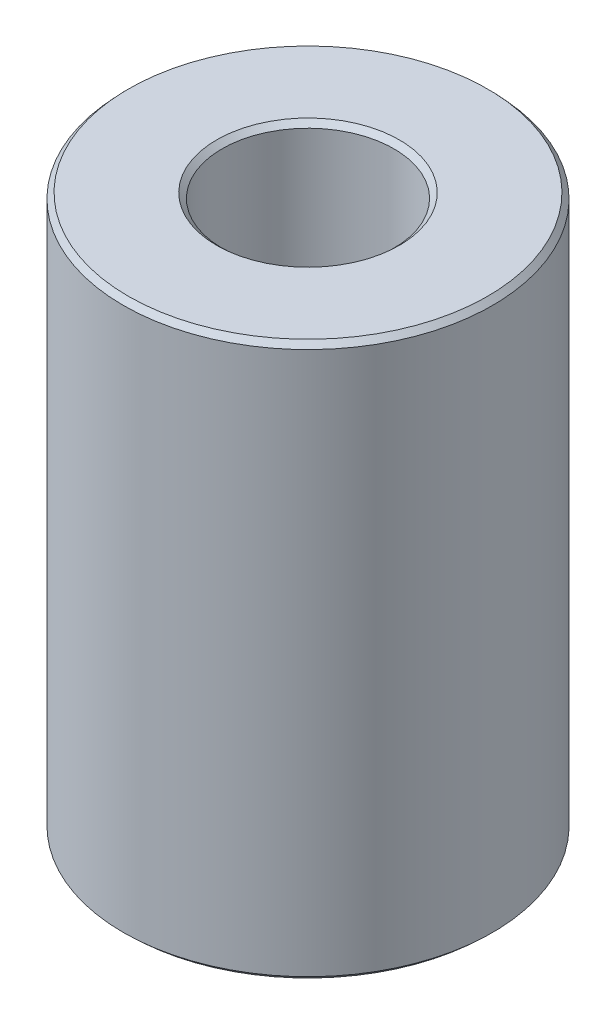
SolidWorks part; units mm, degrees
ref_plane "Front Plane" through (0, 0, 0) normal (0, 0, 1) x (1, 0, 0)
ref_plane "Top Plane" through (0, 0, 0) normal (0, 1, 0) x (1, 0, 0)
ref_plane "Right Plane" through (0, 0, 0) normal (1, 0, 0) x (0, 0, -1)
sketch "Sketch1" plane through (0, 0, 0) normal (0, 1, 0) x (1, 0, 0)
  circle A0 centre (0, 0) radius 47.5
  dimension "SLEEVE_OD" = 95
extrude "Boss-Extrude1" add sketch "Sketch1" along normal blind 142.4217
sketch "Sketch2" plane through (0, 0, 0) normal (0, 1, 0) x (1, 0, 0)
  circle A0 centre (0, 0) radius 22.1284
  dimension "BORE_D" = 44.2568
extrude "Cut-Extrude1" cut sketch "Sketch2" along normal through all
chamfer "Chamfer1" distance 1.3935 angle 42.797 4 edges at (0, 142.4217, 22.1284) (0, 0, 22.1284) (0, 0, 47.5) (0, 142.4217, 47.5) first distance on face at (0, 142.4217, 22.1284) first distance on face at (0, 0, 22.1284) first distance on face at (0, 142.4217, 47.5)
